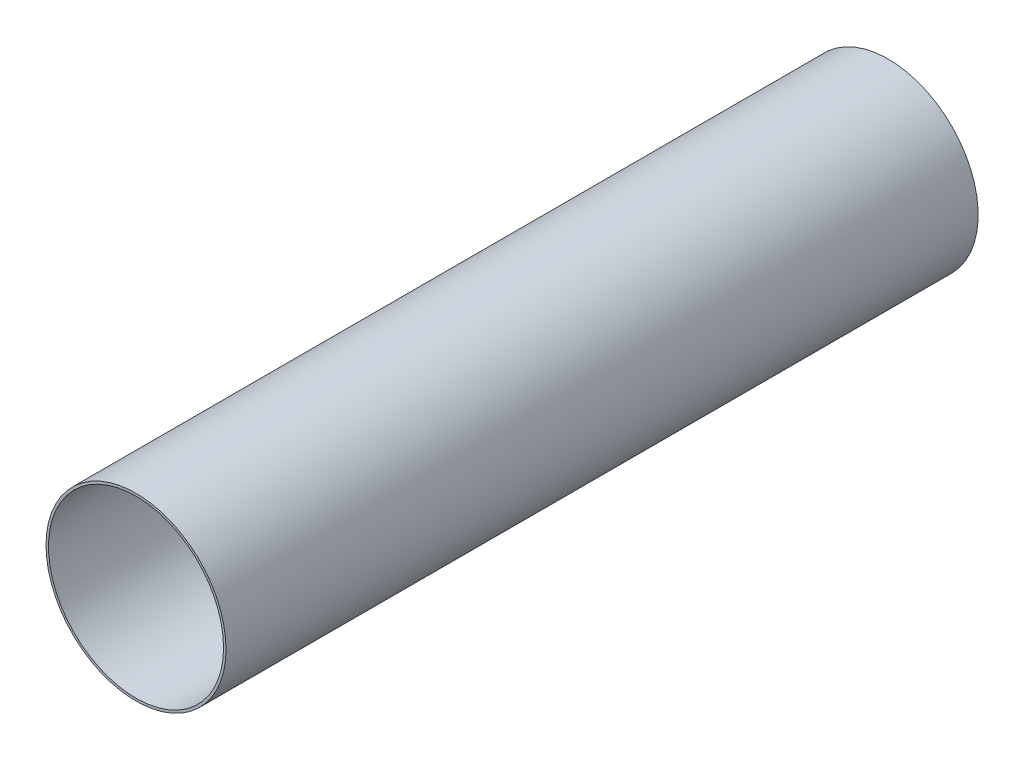
SolidWorks part; units mm, degrees
material "PVC Rigid"
ref_plane "Front Plane" through (0, 0, 0) normal (0, 0, 1) x (1, 0, 0)
ref_plane "Top Plane" through (0, 0, 0) normal (0, 1, 0) x (1, 0, 0)
ref_plane "Right Plane" through (0, 0, 0) normal (1, 0, 0) x (0, 0, -1)
sketch "Sketch1" plane through (0, 0, 0) normal (0, 0, 1) x (1, 0, 0)
  circle A0 centre (0, 0) radius 71
  circle A1 centre (0, 0) radius 73
  dimension "D1" = 142
  dimension "D2" = 146
extrude "Boss-Extrude1" add sketch "Sketch1" along normal blind 608
sketch "Sketch2" plane through (0, 0, 0) normal (0, 0, -1) x (-1, 0, 0)
  circle A0 centre (0, 0) radius 73 construction
  circle A1 centre (0, 0) radius 73
extrude "Boss-Extrude2" add sketch "Sketch2" along normal blind 2
